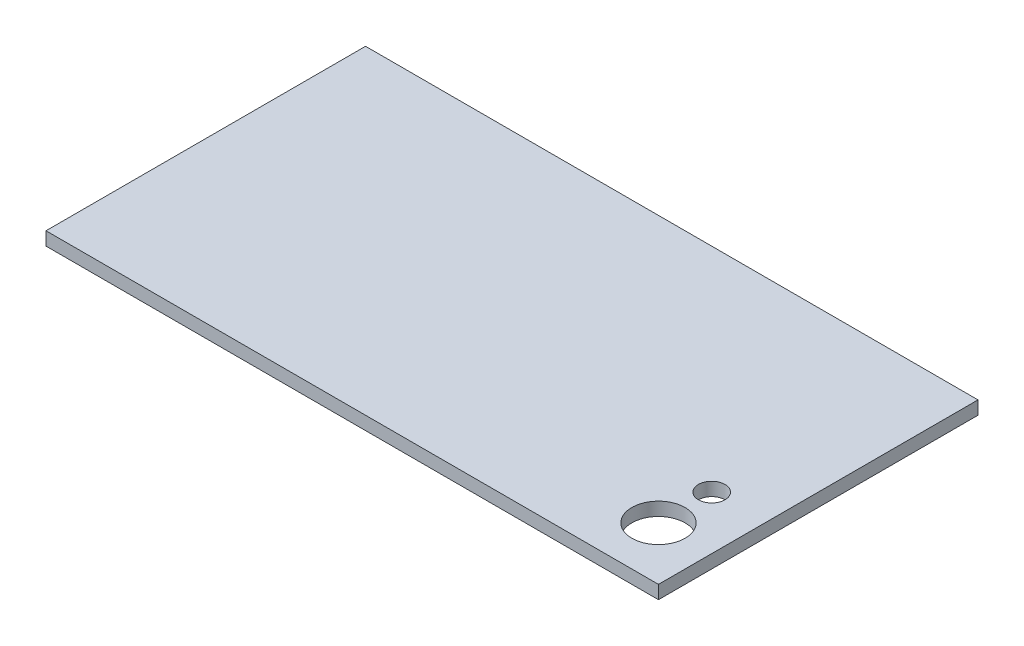
SolidWorks part; units mm, degrees
ref_plane "Front Plane" through (0, 0, 0) normal (0, 0, 1) x (1, 0, 0)
ref_plane "Top Plane" through (0, 0, 0) normal (0, 1, 0) x (1, 0, 0)
ref_plane "Right Plane" through (0, 0, 0) normal (1, 0, 0) x (0, 0, -1)
sketch "Sketch1" plane through (0, 0, 0) normal (0, 1, 0) x (1, 0, 0)
  line L1 (0, 0) -> (146.05, 0)
  line L2 (0, 0) -> (0, 76.2)
  line L3 (0, 76.2) -> (146.05, 76.2)
  line L4 (146.05, 0) -> (146.05, 76.2)
  circle A0 centre (133.35, 12.7) radius 6.35
  circle A1 centre (133.35, 25.4) radius 3.175
  dimension "D3" = 6.35
  dimension "D4" = 12.7
  dimension "D1" = 76.2
  dimension "D2" = 146.05
  dimension "D5" = 12.7
  dimension "D6" = 12.7
  dimension "D7" = 12.7
  dimension "D8" = 12.7
extrude "Boss-Extrude1" add sketch "Sketch1" along normal blind 3.175
